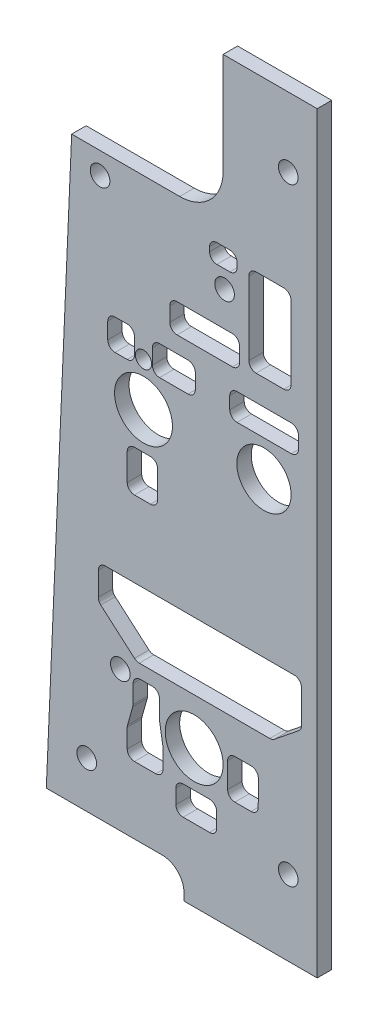
SolidWorks part; units mm, degrees
material "Acrylic (Medium-high impact)"
ref_plane "Front Plane" through (0, 0, 0) normal (0, 0, 1) x (1, 0, 0)
ref_plane "Top Plane" through (0, 0, 0) normal (0, 1, 0) x (1, 0, 0)
ref_plane "Right Plane" through (0, 0, 0) normal (1, 0, 0) x (0, 0, -1)
sketch "Sketch1" plane through (0, 0, 0) normal (0, 0, 1) x (1, 0, 0)
  line L8 (-29.21, 1.5875) -> (-29.21, 0)
  line L9 (-29.21, 0) -> (0, 0)
  line L10 (0, 0) -> (0, 165.1)
  line L11 (0, 165.1) -> (-25.4, 165.1)
  line L12 (-25.4, 165.1) -> (-25.4, 138.1125)
  line L13 (-30.1625, 133.35) -> (-53.848, 133.35)
  line L14 (-53.848, 133.35) -> (-59.4118, 6.35)
  line L15 (-59.4118, 6.35) -> (-33.9725, 6.35)
  line L16 (-29.21, 1.5875) -> (-29.21, 0)
  line L17 (-29.21, 0) -> (0, 0)
  line L18 (0, 0) -> (0, 165.1)
  line L19 (0, 165.1) -> (-25.4, 165.1)
  line L20 (-25.4, 165.1) -> (-25.4, 138.1125)
  line L21 (-30.1625, 133.35) -> (-53.848, 133.35)
  line L22 (-53.848, 133.35) -> (-59.4118, 6.35)
  line L23 (-59.4118, 6.35) -> (-33.9725, 6.35)
  arc A2 (-29.21, 1.5875) -> (-33.9725, 6.35) centre (-33.9725, 1.5875) ccw
  arc A3 (-30.1625, 133.35) -> (-25.4, 138.1125) centre (-30.1625, 138.1125) ccw
  arc A4 (-29.21, 1.5875) -> (-33.9725, 6.35) centre (-33.9725, 1.5875) ccw
  arc A5 (-30.1625, 133.35) -> (-25.4, 138.1125) centre (-30.1625, 138.1125) ccw
  dimension "D1" = 0
extrude "Boss-Extrude1" add sketch "Sketch1" against normal blind 3.175
hole_wizard "#6 Clearance Hole1" positions "Sketch3" profile "Sketch2" hole size "#6" standard "ANSI Inch" end condition through all
sketch "Sketch3" plane through (0, 0, 0) normal (0, 0, 1) x (1, 0, 0)
  point P0 (-47.625, 128.5875)
  point P3 (-6.35, 149.86)
  point P6 (-50.546, 16.51)
  point P9 (-6.35, 16.51)
sketch "Sketch2" plane through (-47.625, 128.5875, 0) normal (1, 0, 0) x (0, -1, 0)
  line L0 (0, 0) -> (0, 3.175)
  line L1 (0, 3.175) -> (2.1526, 3.175)
  line L2 (2.1526, 3.175) -> (2.1526, 0)
  line L5 (2.1526, 0) -> (0, 0)
  line L11 (0, -6.35) -> (0, 107.95) construction
  dimension "Thru Hole Dia." = 4.3053
  dimension "Thru Hole Depth" = 3.175
hole_wizard "#6 Clearance Hole2" positions "Sketch5" profile "Sketch4" hole size "#6" standard "ANSI Inch" end condition through all
sketch "Sketch5" plane through (0, 0, 0) normal (0, 0, 1) x (1, 0, 0)
  point P0 (-43.18, 37.084)
  point P3 (-20.32, 120.65)
sketch "Sketch4" plane through (-43.18, 37.084, 0) normal (1, 0, 0) x (0, -1, 0)
  line L0 (0, 0) -> (0, 3.175)
  line L1 (0, 3.175) -> (2.1526, 3.175)
  line L2 (2.1526, 3.175) -> (2.1526, 0)
  line L5 (2.1526, 0) -> (0, 0)
  line L11 (0, -6.35) -> (0, 107.95) construction
  dimension "Thru Hole Dia." = 4.3053
  dimension "Thru Hole Depth" = 3.175
hole_wizard "9/64 (0.14063) Diameter Hole1" positions "Sketch7" profile "Sketch6" hole size "9/64" standard "ANSI Inch" end condition through all
sketch "Sketch7" plane through (0, 0, 0) normal (0, 0, 1) x (1, 0, 0)
  point P0 (-38.1, 98.425)
  point P3 (-36.5125, 30.1625)
sketch "Sketch6" plane through (-38.1, 98.425, 0) normal (1, 0, 0) x (0, -1, 0)
  line L0 (0, 0) -> (0, 3.175)
  line L1 (0, 3.175) -> (1.786, 3.175)
  line L2 (1.786, 3.175) -> (1.786, 0)
  line L5 (1.786, 0) -> (0, 0)
  line L11 (0, -6.35) -> (0, 107.95) construction
  dimension "Thru Hole Dia." = 3.572
  dimension "Thru Hole Depth" = 3.175
hole_wizard "15/32 (0.46875) Diameter Hole1" positions "Sketch9" profile "Sketch8" hole size "15/32" standard "ANSI Inch" end condition through all
sketch "Sketch9" plane through (0, 0, 0) normal (0, 0, 1) x (1, 0, 0)
  point P0 (-11.684, 88.9)
sketch "Sketch8" plane through (-11.684, 88.9, 0) normal (1, 0, 0) x (0, -1, 0)
  line L0 (0, 0) -> (0, 3.175)
  line L1 (0, 3.175) -> (5.9531, 3.175)
  line L2 (5.9531, 3.175) -> (5.9531, 0)
  line L5 (5.9531, 0) -> (0, 0)
  line L11 (0, -6.35) -> (0, 107.95) construction
  dimension "Thru Hole Dia." = 11.9062
  dimension "Thru Hole Depth" = 3.175
hole_wizard "1/2 (0.5) Diameter Hole1" positions "Sketch11" profile "Sketch10" hole size "1/2" standard "ANSI Inch" end condition through all
sketch "Sketch11" plane through (0, 0, 0) normal (0, 0, 1) x (1, 0, 0)
  point P0 (-38.1, 88.9)
  point P3 (-26.9875, 30.1625)
sketch "Sketch10" plane through (-38.1, 88.9, 0) normal (1, 0, 0) x (0, -1, 0)
  line L0 (0, 0) -> (0, 3.175)
  line L1 (0, 3.175) -> (6.35, 3.175)
  line L2 (6.35, 3.175) -> (6.35, 0)
  line L5 (6.35, 0) -> (0, 0)
  line L11 (0, -6.35) -> (0, 107.95) construction
  dimension "Thru Hole Dia." = 12.7
  dimension "Thru Hole Depth" = 3.175
sketch "Sketch12" plane through (0, 0, 0) normal (0, 0, 1) x (1, 0, 0)
  line L0 (0, 165.1) -> (-25.4, 165.1) construction
  line L1 (-20.6375, 165.1) -> (-30.1625, 165.1)
  line L2 (-20.6375, 165.1) -> (-20.6375, 133.35)
  line L3 (-20.6375, 133.35) -> (-30.1625, 133.35)
  line L4 (-30.1625, 165.1) -> (-30.1625, 133.35)
  line L5 (-25.4, 165.1) -> (-25.4, 138.1125) construction
  dimension "D1" = 4.7625
extrude "Cut-Extrude1" cut sketch "Sketch12" against normal up to next
fillet "Fillet1" radius 9.525 1 edges at (-20.6375, 133.35, -1.5875)
sketch "Sketch13" plane through (0, 0, 0) normal (0, 0, 1) x (1, 0, 0)
  line L0 (-30.7478, 113.0864) -> (-18.616, 113.0864)
  line L1 (-17.0285, 111.4989) -> (-17.0285, 108.3583)
  line L2 (-18.616, 106.7708) -> (-30.7478, 106.7708)
  line L3 (-32.3353, 108.3583) -> (-32.3353, 111.4989)
  line L4 (-34.5742, 103.1949) -> (-28.3255, 103.1949)
  line L5 (-26.738, 101.6074) -> (-26.738, 98.3259)
  line L6 (-28.3255, 96.7384) -> (-34.5742, 96.7384)
  line L7 (-36.1617, 98.3259) -> (-36.1617, 101.6074)
  line L8 (-40.0808, 98.225) -> (-40.0808, 101.7856)
  line L9 (-41.6683, 103.3731) -> (-44.3528, 103.3731)
  line L10 (-45.9403, 101.7856) -> (-45.9403, 98.225)
  line L11 (-44.3528, 96.6375) -> (-41.6683, 96.6375)
  line L12 (-40.0808, 80.7593) -> (-36.5751, 80.7593)
  line L13 (-34.9876, 79.1718) -> (-34.9876, 73.2877)
  line L14 (-36.5751, 71.7002) -> (-40.0808, 71.7002)
  line L15 (-41.6683, 73.2877) -> (-41.6683, 79.1718)
  line L16 (-17.5944, 102.5821) -> (-5.696, 102.5821)
  line L17 (-4.1085, 100.9946) -> (-4.1085, 98.3259)
  line L18 (-5.696, 96.7384) -> (-17.5944, 96.7384)
  line L19 (-19.1819, 98.3259) -> (-19.1819, 100.9946)
  line L20 (-48.0191, 53.4281) -> (-48.0191, 48.2949)
  line L21 (-47.4716, 47.0956) -> (-40.0723, 40.6793)
  line L22 (-39.0322, 40.2911) -> (-10.3944, 40.2911)
  line L23 (-9.3988, 40.6421) -> (-4.0444, 44.953)
  line L24 (-3.4525, 46.1896) -> (-3.4525, 53.4281)
  line L25 (-5.04, 55.0156) -> (-46.4316, 55.0156)
  line L26 (-40.3845, 35.7367) -> (-40.3845, 31.7652)
  line L28 (-34.5742, 31.6755) -> (-34.5742, 35.7367)
  line L29 (-36.1617, 37.3242) -> (-38.797, 37.3242)
  line L31 (-33.8284, 26.8634) -> (-33.8284, 22.6726)
  line L32 (-35.4159, 21.0851) -> (-40.0766, 21.0851)
  line L33 (-41.6641, 22.6726) -> (-41.6641, 26.7737)
  line L34 (-29.4065, 22.1594) -> (-23.6235, 22.1594)
  line L35 (-22.036, 20.5719) -> (-22.036, 17.4274)
  line L36 (-23.6235, 15.8399) -> (-29.4065, 15.8399)
  line L37 (-30.994, 17.4274) -> (-30.994, 20.5719)
  line L38 (-19.6522, 31.4531) -> (-19.6522, 25.9613)
  line L39 (-18.0647, 24.3738) -> (-14.5239, 24.3738)
  line L40 (-12.9364, 25.953) -> (-12.9075, 31.4447)
  line L41 (-22.0171, 128.678) -> (-19.1528, 128.678)
  line L42 (-14.4949, 33.0406) -> (-18.0647, 33.0406)
  line L43 (-17.5653, 127.0905) -> (-17.5653, 126.1194)
  line L44 (-40.4437, 31.3357) -> (-41.6049, 27.2032)
  line L45 (-34.5533, 31.4189) -> (-33.8493, 27.12)
  line L46 (-19.1528, 124.5319) -> (-22.0171, 124.5319)
  line L47 (-23.6046, 126.1194) -> (-23.6046, 127.0905)
  line L48 (-13.4065, 127.4034) -> (-7.3284, 127.4034)
  line L49 (-5.7409, 125.8159) -> (-5.7409, 109.7543)
  line L50 (-7.3284, 108.1668) -> (-13.4065, 108.1668)
  line L51 (-14.994, 109.7543) -> (-14.994, 125.8159)
  arc A0 (-18.616, 113.0864) -> (-17.0285, 111.4989) centre (-18.616, 111.4989) cw
  arc A1 (-17.0285, 108.3583) -> (-18.616, 106.7708) centre (-18.616, 108.3583) cw
  arc A2 (-30.7478, 106.7708) -> (-32.3353, 108.3583) centre (-30.7478, 108.3583) cw
  arc A3 (-30.7478, 113.0864) -> (-32.3353, 111.4989) centre (-30.7478, 111.4989) ccw
  arc A5 (-34.5742, 96.7384) -> (-36.1617, 98.3259) centre (-34.5742, 98.3259) cw
  arc A6 (-26.738, 98.3259) -> (-28.3255, 96.7384) centre (-28.3255, 98.3259) cw
  arc A7 (-28.3255, 103.1949) -> (-26.738, 101.6074) centre (-28.3255, 101.6074) cw
  arc A8 (-36.1617, 101.6074) -> (-34.5742, 103.1949) centre (-34.5742, 101.6074) cw
  arc A9 (-40.0808, 101.7856) -> (-41.6683, 103.3731) centre (-41.6683, 101.7856) ccw
  arc A10 (-45.9403, 98.225) -> (-44.3528, 96.6375) centre (-44.3528, 98.225) ccw
  arc A11 (-44.3528, 103.3731) -> (-45.9403, 101.7856) centre (-44.3528, 101.7856) ccw
  arc A12 (-40.0808, 98.225) -> (-41.6683, 96.6375) centre (-41.6683, 98.225) cw
  arc A13 (-40.0808, 71.7002) -> (-41.6683, 73.2877) centre (-40.0808, 73.2877) cw
  arc A14 (-34.9876, 73.2877) -> (-36.5751, 71.7002) centre (-36.5751, 73.2877) cw
  arc A15 (-36.5751, 80.7593) -> (-34.9876, 79.1718) centre (-36.5751, 79.1718) cw
  arc A16 (-40.0808, 80.7593) -> (-41.6683, 79.1718) centre (-40.0808, 79.1718) ccw
  arc A17 (-5.696, 102.5821) -> (-4.1085, 100.9946) centre (-5.696, 100.9946) cw
  arc A18 (-4.1085, 98.3259) -> (-5.696, 96.7384) centre (-5.696, 98.3259) cw
  arc A19 (-17.5944, 96.7384) -> (-19.1819, 98.3259) centre (-17.5944, 98.3259) cw
  arc A20 (-17.5944, 102.5821) -> (-19.1819, 100.9946) centre (-17.5944, 100.9946) ccw
  arc A21 (-3.4525, 53.4281) -> (-5.04, 55.0156) centre (-5.04, 53.4281) ccw
  arc A22 (-4.0444, 44.953) -> (-3.4525, 46.1896) centre (-5.04, 46.1896) ccw
  arc A23 (-10.3944, 40.2911) -> (-9.3988, 40.6421) centre (-10.3944, 41.8786) ccw
  arc A24 (-48.0191, 48.2949) -> (-47.4716, 47.0956) centre (-46.4316, 48.2949) ccw
  arc A25 (-40.0723, 40.6793) -> (-39.0322, 40.2911) centre (-39.0322, 41.8786) ccw
  arc A26 (-48.0191, 53.4281) -> (-46.4316, 55.0156) centre (-46.4316, 53.4281) cw
  arc A27 (-34.5742, 35.7367) -> (-36.1617, 37.3242) centre (-36.1617, 35.7367) ccw
  arc A30 (-40.3845, 35.7367) -> (-38.797, 37.3242) centre (-38.797, 35.7367) cw
  arc A31 (-40.0766, 21.0851) -> (-41.6641, 22.6726) centre (-40.0766, 22.6726) cw
  arc A32 (-33.8284, 22.6726) -> (-35.4159, 21.0851) centre (-35.4159, 22.6726) cw
  arc A35 (-29.4065, 15.8399) -> (-30.994, 17.4274) centre (-29.4065, 17.4274) cw
  arc A36 (-22.036, 17.4274) -> (-23.6235, 15.8399) centre (-23.6235, 17.4274) cw
  arc A37 (-23.6235, 22.1594) -> (-22.036, 20.5719) centre (-23.6235, 20.5719) cw
  arc A38 (-29.4065, 22.1594) -> (-30.994, 20.5719) centre (-29.4065, 20.5719) ccw
  arc A39 (-12.9075, 31.4447) -> (-14.4949, 33.0406) centre (-14.4949, 31.4531) ccw
  arc A40 (-14.5239, 24.3738) -> (-12.9364, 25.953) centre (-14.5239, 25.9613) ccw
  arc A41 (-19.6522, 25.9613) -> (-18.0647, 24.3738) centre (-18.0647, 25.9613) ccw
  arc A42 (-19.6522, 31.4531) -> (-18.0647, 33.0406) centre (-18.0647, 31.4531) cw
  arc A44 (-34.5742, 31.6755) -> (-34.5533, 31.4189) centre (-32.9867, 31.6755) ccw
  arc A45 (-33.8284, 26.8634) -> (-33.8493, 27.12) centre (-35.4159, 26.8634) ccw
  arc A46 (-41.6641, 26.7737) -> (-41.6049, 27.2032) centre (-40.0766, 26.7737) cw
  arc A47 (-40.3845, 31.7652) -> (-40.4437, 31.3357) centre (-41.972, 31.7652) cw
  arc A48 (-17.5653, 126.1194) -> (-19.1528, 124.5319) centre (-19.1528, 126.1194) cw
  arc A49 (-19.1528, 128.678) -> (-17.5653, 127.0905) centre (-19.1528, 127.0905) cw
  arc A50 (-22.0171, 128.678) -> (-23.6046, 127.0905) centre (-22.0171, 127.0905) ccw
  arc A51 (-22.0171, 124.5319) -> (-23.6046, 126.1194) centre (-22.0171, 126.1194) cw
  arc A52 (-5.7409, 109.7543) -> (-7.3284, 108.1668) centre (-7.3284, 109.7543) cw
  arc A53 (-7.3284, 127.4034) -> (-5.7409, 125.8159) centre (-7.3284, 125.8159) cw
  arc A54 (-13.4065, 127.4034) -> (-14.994, 125.8159) centre (-13.4065, 125.8159) ccw
  arc A55 (-13.4065, 108.1668) -> (-14.994, 109.7543) centre (-13.4065, 109.7543) cw
  point P122 (-12.899, 33.0406)
  dimension "D1" = 1.5875
  dimension "D2" = 1.5875
  dimension "D3" = 1.5875
  dimension "D4" = 1.5875
  dimension "D5" = 1.5875
  dimension "D6" = 1.5875
  dimension "D7" = 1.5875
  dimension "D8" = 1.5875
  dimension "D9" = 1.5875
  dimension "D10" = 1.5875
  dimension "D11" = 1.5875
  dimension "D12" = 1.5875
  dimension "D13" = 1.5875
extrude "Cut-Extrude2" cut sketch "Sketch13" against normal through all
